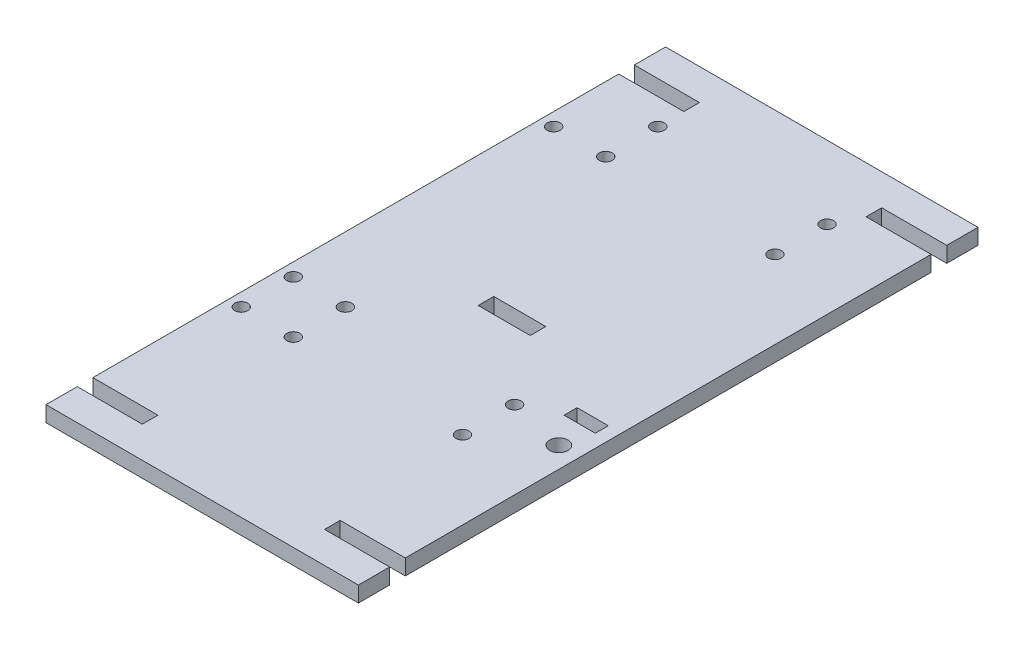
SolidWorks part; units mm, degrees
ref_plane "Front" through (0, 0, 0) normal (0, 0, 1) x (1, 0, 0)
ref_plane "Top" through (0, 0, 0) normal (0, 1, 0) x (1, 0, 0)
ref_plane "Right" through (0, 0, 0) normal (1, 0, 0) x (0, 0, -1)
sketch "Sketch1" plane through (0, 0, 0) normal (0, 1, 0) x (1, 0, 0)
  line L1 (0, 0) -> (-120, 0)
  line L2 (0, 0) -> (0, 238)
  line L3 (0, 238) -> (-120, 238)
  line L4 (-120, 0) -> (-120, 238)
  dimension "D1" = 238
  dimension "D2" = 120
extrude "Boss-Extrude1" add sketch "Sketch1" along normal blind 6
sketch "Sketch2" plane through (0, 6, 0) normal (0, 1, 0) x (1, 0, 0)
  line L0 (-120, 238) -> (-120, 0) construction
  line L1 (-120, 226) -> (-95, 226)
  line L2 (-120, 226) -> (-120, 220)
  line L3 (-120, 220) -> (-95, 220)
  line L4 (-95, 226) -> (-95, 220)
  line L5 (0, 238) -> (-120, 238) construction
  dimension "D1" = 6
  dimension "D2" = 25
  dimension "D3" = 12
extrude "Cut-Extrude1" cut sketch "Sketch2" against normal through all
pattern_linear "LPattern1" count 2 spacing 208 along (0, 0, 1) count 2 spacing 95 along (1, 0, 0) of "Cut-Extrude1"
sketch "Sketch3" plane through (0, 6, 0) normal (0, 1, 0) x (1, 0, 0)
  line L0 (-60, 238) -> (-60, 0) construction
  line L1 (0, 238) -> (-120, 238) construction
  line L2 (-120, 0) -> (0, 0) construction
  line L3 (-120, 119) -> (0, 119) construction
  line L4 (-120, 220) -> (-120, 18) construction
  line L5 (0, 18) -> (0, 220) construction
  line L7 (-70, 116) -> (-50, 116)
  line L8 (-70, 116) -> (-70, 122)
  line L9 (-70, 122) -> (-50, 122)
  line L10 (-50, 116) -> (-50, 122)
  line L11 (-70, 116) -> (-50, 122) construction
  line L12 (-70, 122) -> (-50, 116) construction
  point P12 (-60, 119)
  dimension "D1" = 6
  dimension "D2" = 20
extrude "Cut-Extrude2" cut sketch "Sketch3" against normal blind 10
sketch "Sketch4" plane through (0, 6, 0) normal (0, 1, 0) x (1, 0, 0)
  line L0 (-105, 90) -> (-105, 190) construction
  line L1 (-30, 210) -> (-30, 190) construction
  line L2 (-95, 200) -> (-30, 200) construction
  line L3 (-95, 80) -> (-30, 80) construction
  line L4 (-70, 116) -> (-50, 116) construction
  line L5 (-105, 80) -> (-105, 30) construction
  line L6 (-120, 220) -> (-120, 18) construction
  line L7 (-115, 90) -> (-95, 90) construction
  line L8 (-95, 90) -> (-95, 70) construction
  line L9 (-30, 90) -> (-30, 70) construction
  line L10 (-115, 90) -> (-115, 70) construction
  line L11 (-115, 70) -> (-95, 70) construction
  arc A0 (-105, 90) -> (-95, 80) centre (-95, 90) ccw construction
  arc A1 (-105, 190) -> (-95, 200) centre (-95, 190) cw construction
  circle A2 centre (-30, 210) radius 2.5
  circle A3 centre (-30, 190) radius 2.5
  circle A4 centre (-95, 210) radius 2.5
  circle A5 centre (-95, 190) radius 2.5
  circle A6 centre (-115, 190) radius 2.5
  circle A13 centre (-95, 90) radius 2.5
  circle A14 centre (-115, 90) radius 2.5
  circle A15 centre (-95, 70) radius 2.5
  circle A16 centre (-30, 90) radius 2.5
  circle A17 centre (-30, 70) radius 2.5
  circle A18 centre (-115, 70) radius 2.5
  point P11 (-120, 119)
  point P15 (-105, 200)
  point P17 (-95, 200)
  point P18 (-105, 190)
  point P19 (-105, 90)
  point P20 (-95, 80)
  point P21 (-30, 80)
  point P23 (-30, 200)
  point P26 (-95, 80)
  point P32 (-105, 90)
  point P35 (-95, 190)
  point P39 (-30, 80)
  dimension "D6" = 10
  dimension "D7" = 5
  dimension "D1" = 36
  dimension "D2" = 50
  dimension "D3" = 75
  dimension "D4" = 15
  dimension "D5" = 120
  dimension "D8" = 20
  dimension "D9" = 2
  dimension "D10" = 2
extrude "Cut-Extrude4" cut sketch "Sketch4" against normal blind 10
sketch "Sketch6" plane through (0, 6, 0) normal (0, 1, 0) x (1, 0, 0)
  line L0 (0, 18) -> (0, 220) construction
  line L1 (-5, 101) -> (-17, 101)
  line L2 (-5, 101) -> (-5, 96)
  line L3 (-5, 96) -> (-17, 96)
  line L4 (-17, 101) -> (-17, 96)
  line L5 (-70, 116) -> (-50, 116) construction
  circle A0 centre (-8, 85) radius 3.5
  dimension "D5" = 11
  dimension "D6" = 3
  dimension "D7" = 7
  dimension "D1" = 5
  dimension "D2" = 12
  dimension "D3" = 5
  dimension "D4" = 15
extrude "Cut-Extrude5" cut sketch "Sketch6" against normal blind 10
